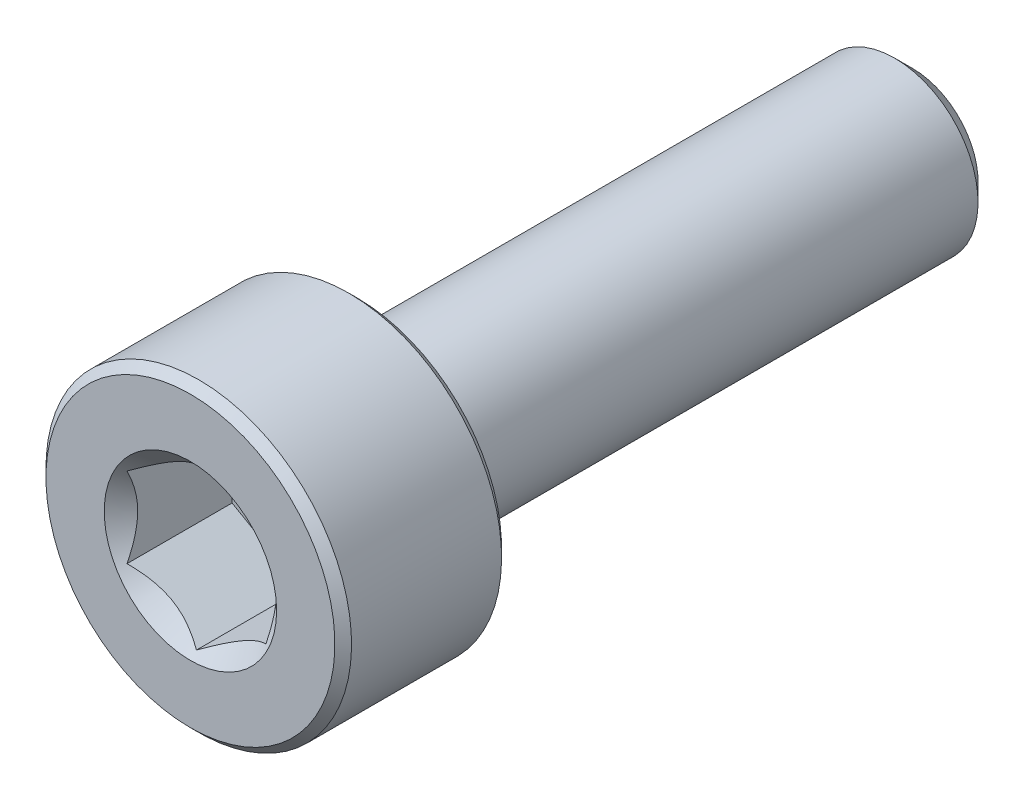
SolidWorks part; units mm, degrees
ref_plane "Front Plane" through (0, 0, 0) normal (0, 0, 1) x (1, 0, 0)
ref_plane "Top Plane" through (0, 0, 0) normal (0, 1, 0) x (1, 0, 0)
ref_plane "Right Plane" through (0, 0, 0) normal (1, 0, 0) x (0, 0, -1)
sketch "Sketch1" plane through (0, 0, 0) normal (1, 0, 0) x (0, 0, -1)
  line L0 (-6.5, 0) -> (6.5, 0) construction
  line L1 (6.5, 0) -> (6.5, 1.1752) construction
  line L2 (6.5, 1.1752) -> (6.1752, 1.5) construction
  line L3 (6.1752, 1.5) -> (6.125, 1.5) construction
  line L4 (6.125, 1.5) -> (-3.5, 1.5) construction
  line L5 (-3.5, 1.5) -> (-3.5, 2.75) construction
  line L6 (-3.5, 2.75) -> (-6.5, 2.75) construction
  line L7 (-6.5, 2.75) -> (-6.5, 0) construction
  line L8 (6.5, 1.1752) -> (6.5, 1.5) construction
  line L9 (6.4688, 1.5541) -> (6.7188, 1.1211) construction
  line L10 (6.7188, 1.1211) -> (6.9687, 1.5541) construction
  line L11 (6.9687, 1.5541) -> (6.4688, 1.5541) construction
  line L12 (6.7188, 1.5541) -> (6.7188, 1.5) construction
  line L13 (6.7188, 1.1211) -> (6.7188, 1.1752) construction
  line L14 (6.6875, 1.1752) -> (6.75, 1.1752) construction
  line L15 (6.5, 1.5) -> (6.9375, 1.5) construction
  line L16 (6.4844, 1.5271) -> (6.9531, 1.5271) construction
  line L17 (6.5, 0) -> (6.5, -1.5) construction
  line L18 (-3.65, 2.75) -> (-3.5, 2.6) construction
  line L19 (-6.35, 2.75) -> (-6.5, 2.6) construction
  line L20 (-3.5, 1.5) -> (-3.5, 0) construction
  line L21 (-3.5, 0.75) -> (-0.1667, 0.75) construction
  line L22 (-0.1667, 0.75) -> (3.1667, 0.75) construction
  line L23 (3.1667, 0.75) -> (6.5, 0.75) construction
  line L24 (-0.1667, 0.75) -> (-0.1667, 1.5) construction
  line L25 (-0.1667, 1.5) -> (-0.1667, 2.75) construction
  line L26 (3.1667, 0.75) -> (3.1667, 2.75) construction
  point P0 (-6.5, 1.25)
  point P3 (5.25, 1.5)
  point P4 (0, 0)
  point P18 (3.1667, 1.5)
  point P22 (6.7188, 1.1752)
  point P24 (6.125, 1.5)
  point P25 (6.7188, 1.5)
  point P28 (6.7187, 1.5271)
  point P29 (5.25, -1.5)
  point P30 (-0.1667, 1.5)
  point P31 (-5, 2.75)
  point P37 (-4.025, 2.75)
  point P38 (-6.275, 2.75)
  point P45 (-0.1667, 0.75)
  point P46 (3.1667, 0.75)
  dimension "D2" = 0.0625
  dimension "D7" = 0.15
  dimension "D8" = 0.15
  dimension "D9" = 0.15
  dimension "D10" = 0.075
  dimension "D11" = 0.375
  dimension "Drive Size" = 2.5
  dimension "Head Diameter" = 5.5
  dimension "Head Height" = 3
  dimension "Thread Pitch" = 0.5
  dimension "Thread Dia" = 3
  dimension "Length" = 10
  dimension "D12" = 0.375
  dimension "D4" = 1.25
  dimension "D3" = 45
sketch "Sketch2" plane through (0, 0, 0) normal (1, 0, 0) x (0, 0, -1)
  line L0 (-6.5, 0) -> (-6.5, 2.6)
  line L1 (-6.35, 2.75) -> (-3.65, 2.75)
  line L2 (-3.5, 2.6) -> (-3.5, 1.65)
  line L4 (6.1752, 1.5) -> (6.5, 1.1752)
  line L5 (6.5, 1.1752) -> (6.5, 0)
  line L6 (-3.5, 2.75) -> (-6.5, 2.75) construction
  line L7 (6.5, 0) -> (-6.5, 0)
  line L8 (-6.35, 2.75) -> (-6.5, 2.6) construction
  line L10 (-6.35, 2.75) -> (-6.5, 2.6)
  line L14 (-3.65, 2.75) -> (-3.5, 2.6) construction
  line L16 (-3.65, 2.75) -> (-3.5, 2.6)
  line L17 (-3.5, 1.5) -> (-3.5, 2.75) construction
  line L19 (-3.35, 1.5) -> (6.1752, 1.5)
  line L20 (6.125, 1.5) -> (-3.5, 1.5) construction
  arc A1 (-3.5, 1.65) -> (-3.35, 1.5) centre (-3.35, 1.65) ccw
  dimension "D3" = 0.15
revolve "Revolve1" add sketch "Sketch2" angle 360 about L7
sketch "Sketch3" plane through (0, 0, 6.5) normal (0, 0, 1) x (1, 0, 0)
  line L1 (1.25, -0.7217) -> (1.25, 0.7217)
  line L2 (1.25, 0.7217) -> (0, 1.4434)
  line L3 (0, 1.4434) -> (-1.25, 0.7217)
  line L4 (-1.25, 0.7217) -> (-1.25, -0.7217)
  line L5 (-1.25, -0.7217) -> (0, -1.4434)
  line L6 (0, -1.4434) -> (1.25, -0.7217)
  circle A0 centre (0, 0) radius 1.25 construction
  circle A1 centre (0, 0) radius 2.75 construction
  circle A2 centre (0, 0) radius 2.75 construction
  circle A3 centre (0, 0) radius 1.4434 construction
  point P13 (0, 0)
  dimension "D1" = 2.8868
extrude "Cut-Extrude1" cut sketch "Sketch3" against normal offset from surface (2 mm away) 1 up to face at (0, 2.6, 3.5)
sketch "Sketch4" plane through (0, 0, 6.5) normal (0, 0, 1) x (1, 0, 0)
  circle A0 centre (0, 0) radius 1.5516
  dimension "D1" = 3.1033
extrude "Cut-Extrude2" cut sketch "Sketch4" against normal up to vertex (1.5 mm away) draft 45 up to point (0, 2.75, 5)
sketch "Sketch11" plane through (0, 0, 0) normal (1, 0, 0) x (0, 0, -1)
  line L0 (-6.5, 0) -> (6.5, 0) construction
  line L1 (-6.5, 0) -> (6.5, 0) construction
  line L2 (-1.625, 0) -> (-1.625, 1.5) construction
  line L3 (6.125, 1.5) -> (-3.5, 1.5) construction
  line L4 (4.625, 0) -> (4.625, 1.5) construction
  line L6 (6.5, 1.1752) -> (6.5, 1.5) construction
  point P2 (-1.625, 0)
  point P3 (4.625, 0)
  dimension "D1" = 1.875
  dimension "D2" = 1.875
sketch "Sketch6" [suppressed] plane through (0, 0, -6.5) normal (0, 0, -1) x (-1, 0, 0)
  circle A0 centre (0, 0) radius 1.5
curve "Helix/Spiral1" [suppressed] pitch 0.5 height 10.5 turns 21
sketch "Sketch10" [suppressed] plane through (0, 0, 0) normal (1, 0, 0) x (0, 0, -1)
  line L0 (-3.35, -2.75) -> (-3.35, 2.75)
  line L5 (-6.5, 0) -> (6.5, 0) construction
  line L6 (-3.35, 1.5) -> (-3.35, -1.5) construction
  point P3 (-3.35, 0)
split "Split1" [suppressed] bodies to split 106
sketch "Sketch7" [suppressed] plane through (0, 0, 0) normal (1, 0, 0) x (0, 0, -1)
  line L0 (6.4844, 1.5271) -> (6.9531, 1.5271)
  line L1 (6.9531, 1.5271) -> (6.75, 1.1752)
  line L2 (6.75, 1.1752) -> (6.6875, 1.1752)
  line L3 (6.6875, 1.1752) -> (6.4844, 1.5271)
sweep "Cut-Sweep1" [suppressed] cut profiles "Sketch7" path "Helix/Spiral1"
sketch "Sketch8" [suppressed] plane through (0, 0, 0) normal (1, 0, 0) x (0, 0, -1)
  line L0 (-3.5, 0) -> (-3.5, 1.5)
  line L1 (-3.35, -1.5) -> (-3.35, 1.5) construction
  line L2 (-3.5, 1.5) -> (-3.35, 1.5)
  line L4 (-3.35, 1.5) -> (-2.484, 0)
  line L5 (-2.484, 0) -> (-3.5, 0)
  line L6 (6.125, 1.5) -> (-3.5, 1.5) construction
  line L7 (-6.5, 0) -> (6.5, 0) construction
  dimension "D1" = 60
revolve "Revolve2" [suppressed] add sketch "Sketch8" angle 360 about L5
equation "\"D2@Sketch1\" = \"Thread Pitch@Sketch1\" / 8"
equation "\"D4@Helix/Spiral1\" = \"Thread Pitch@Sketch1\""
equation "\"D7@Sketch1\" = \"Head Height@Sketch1\" * .05"
equation "\"D8@Sketch1\"=\"D7@Sketch1\""
equation "\"D9@Sketch1\"=\"D7@Sketch1\""
equation "\"D10@Sketch1\"=\"D7@Sketch1\"/2"
equation "\"D11@Sketch1\"=\"D10@Sketch1\"*5"
equation "\"D4@Sketch1\"=\"Thread Pitch@Sketch1\"*2.5"
equation "\"D12@Sketch1\"=\"Thread Pitch@Sketch1\"*.75"
equation "\"D3@Helix/Spiral1\"=\"Length@Sketch1\"+\"Thread Pitch@Sketch1\""
equation "\"D3@Sketch2\"=\"Thread Dia@Sketch1\"*0.05"
equation "\"D1@Sketch11\"=\"Length@Sketch1\"*0.1875"
equation "\"D2@Sketch11\"=\"D1@Sketch11\""
equation "\"D1@Sketch4\"=\"D1@Sketch3\"*1.075"
